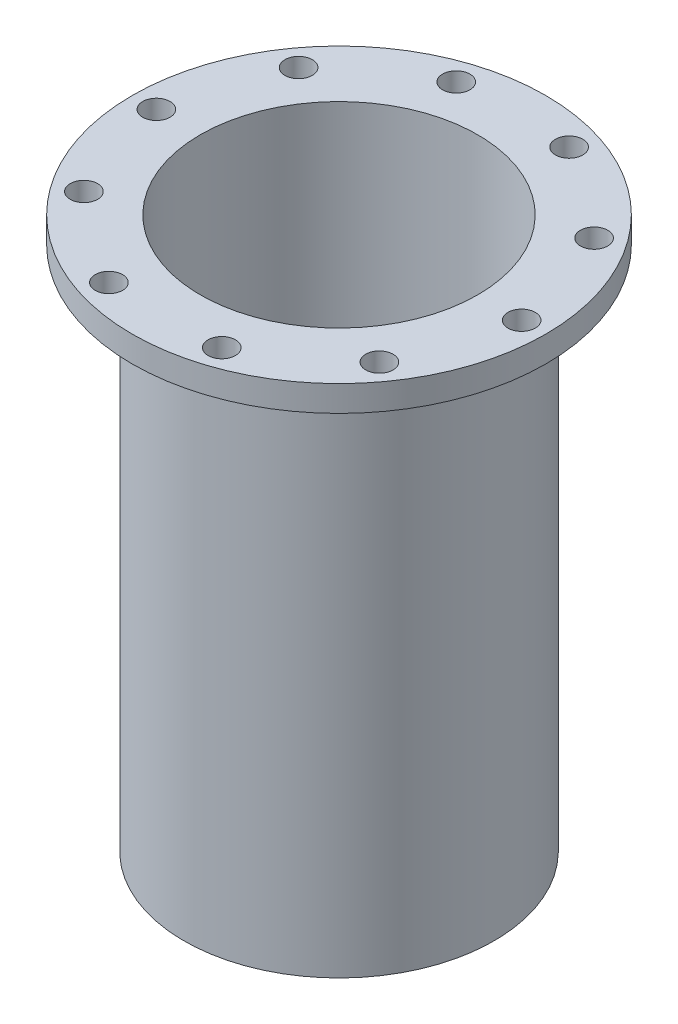
SolidWorks part; units mm, degrees
material "1023 Carbon Steel Sheet (SS)"
ref_plane "Front Plane" through (0, 0, 0) normal (0, 0, 1) x (1, 0, 0)
ref_plane "Top Plane" through (0, 0, 0) normal (0, 1, 0) x (1, 0, 0)
ref_plane "Right Plane" through (0, 0, 0) normal (1, 0, 0) x (0, 0, -1)
sketch "Sketch1" plane through (0, 0, 0) normal (0, 0, 1) x (1, 0, 0)
  line L0 (0, 0) -> (0, -134.8652) construction
  line L2 (51.1302, -203.2) -> (57.15, -203.2)
  line L3 (57.15, -203.2) -> (57.15, -9.525)
  line L4 (57.15, -9.525) -> (76.2, -9.525)
  line L5 (76.2, -9.525) -> (76.2, 0)
  line L6 (76.2, 0) -> (51.1302, 0)
  line L10 (51.1302, -185.42) -> (53.6702, -185.42)
  line L12 (51.1302, 0) -> (51.1302, -185.42)
  line L13 (53.6702, -185.42) -> (53.6702, -190.5)
  line L14 (53.6702, -190.5) -> (51.1302, -190.5)
  line L15 (51.1302, -190.5) -> (51.1302, -203.2)
  dimension "D1" = 51.1302
  dimension "D2" = 57.15
  dimension "D3" = 76.2
  dimension "D4" = 9.525
  dimension "D5" = 203.2
  dimension "D6" = 5.08
  dimension "D7" = 2.54
  dimension "D8" = 12.7
revolve "Revolve1" add sketch "Sketch1" angle 360 about L0
hole_wizard "Tap Drill for 3/8-16 Tap1" positions "Sketch2" profile "Sketch3" hole size "3/8" standard "ANSI Inch" end condition through all
sketch "Sketch2" plane through (0, 0, 0) normal (0, 1, 0) x (1, 0, 0)
  point P1 (67.31, 0)
  dimension "D1" = 67.31
sketch "Sketch3" plane through (67.31, 0, 0) normal (1, 0, 0) x (0, 0, 1)
  line L0 (0, 0) -> (0, 203.2)
  line L1 (0, 203.2) -> (5.0419, 203.2)
  line L2 (5.0419, 203.2) -> (5.0419, 0)
  line L5 (5.0419, 0) -> (0, 0)
  line L11 (0, -6.35) -> (0, 107.95) construction
  dimension "Thru Hole Dia." = 10.0838
  dimension "Thru Hole Depth" = 203.2
pattern_circular "CirPattern1" count 10 over 360 about axis through (0, 0, 0) along (0, 1, 0) of "Tap Drill for 3/8-16 Tap1"
